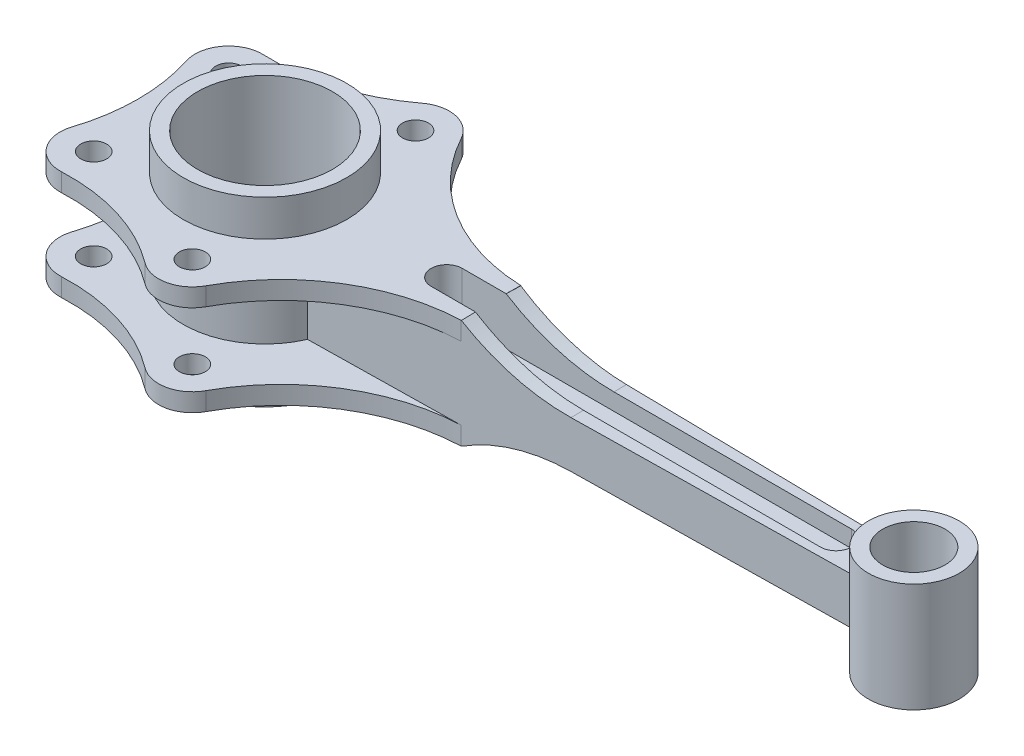
SolidWorks part; units mm, degrees
ref_plane "Front Plane" through (0, 0, 0) normal (0, 0, 1) x (1, 0, 0)
ref_plane "Top Plane" through (0, 0, 0) normal (0, 1, 0) x (1, 0, 0)
ref_plane "Right Plane" through (0, 0, 0) normal (1, 0, 0) x (0, 0, -1)
sketch "Sketch1" plane through (0, 0, 0) normal (0, 0, 1) x (1, 0, 0)
  line L0 (0, 35) -> (0, -35)
  point P0 (0, 0)
  point P7 (0, 0)
  dimension "D3" = 70
sweep "Sweep2" add path "Sketch1" circular profile diameter 63 parameters "D3"=63
sketch "Sketch22" plane through (0, 0, 0) normal (0, 1, 0) x (1, 0, 0)
  line L0 (0, 0) -> (74.8431, 0) construction
  line L1 (0, 13) -> (240, 9)
  line L2 (0, 13) -> (0, -13)
  line L3 (0, -13) -> (240, -9)
  line L5 (240, 9) -> (240, -9)
  point P4 (0, 0)
  point P8 (221.7079, 9)
  dimension "D1" = 26
  dimension "D2" = 18
  dimension "D3" = 240
extrude "Boss-Extrude2" add sketch "Sketch22" along normal mid plane 42
sketch "Sketch34" plane through (0.2166, 0, 12.9964) normal (0.0167, 0, 0.9999) x (0.9999, 0, -0.0167)
  line L0 (28.6932, 21) -> (239.8167, 21) construction
  line L1 (87, 21) -> (243, 21)
  line L2 (128.5692, 9) -> (243, 9)
  line L3 (128.5692, -9) -> (243, -9)
  line L4 (243, 9) -> (243, 21)
  line L5 (0, 0) -> (47.7774, 0) construction
  line L9 (243, -9) -> (243, -21)
  line L10 (87, -21) -> (243, -21)
  arc A0 (87, 21) -> (128.5692, 9) centre (128.5692, 87) ccw
  arc A2 (87, -21) -> (128.5692, -9) centre (128.5692, -87) cw
  point P8 (239.8167, 9)
  point P9 (0, 0)
  point P16 (239.8167, 9)
  point P17 (0, 0)
  point P18 (0, 0)
  point P19 (0, 0)
  dimension "D1" = 87
  dimension "D2" = 78
  dimension "D3" = 9
  dimension "D4" = 156
extrude "Cut-Extrude4" cut sketch "Sketch34" against normal up to next
sketch "Sketch35" plane through (0, 0, 0) normal (0, 0, 1) x (1, 0, 0)
  line L0 (250, 21) -> (250, -21)
  point P2 (250, 0)
  dimension "D1" = 42
  dimension "D2" = 250
sweep "Sweep4" add path "Sketch35" circular profile diameter 35 parameters "D3"=35
sketch "Sketch43" plane through (0, 0, 0) normal (0, 1, 0) x (1, 0, 0)
  line L0 (70, 0) -> (220, 0) construction
  line L1 (70, 6) -> (220, 6)
  line L2 (70, -6) -> (220, -6)
  arc A0 (70, 6) -> (70, -6) centre (70, 0) ccw
  arc A1 (220, -6) -> (220, 6) centre (220, 0) ccw
  circle A2 centre (250, 0) radius 17.5 construction
  circle A3 centre (250, 0) radius 17.5 construction
  point P3 (145, 0)
  dimension "D2" = 6
  dimension "D1" = 150
  dimension "D3" = 30
extrude "Cut-Extrude5" cut sketch "Sketch43" along normal up to next from offset 2.5
mirror "Mirror2" about plane through (0, 0, 0) normal (0, 1, 0) of "Cut-Extrude5"
sketch "Sketch47" plane through (0, 0, 0) normal (0, 1, 0) x (1, 0, 0)
  line L0 (0, 0) -> (17.8892, 0) construction
  line L1 (87, -6) -> (87, -11.55)
  line L2 (70, -6) -> (220, -6) construction
  line L3 (86.9121, 6) -> (70, 6) construction
  line L4 (70, -6) -> (87, -6)
  line L5 (86.9121, 6) -> (70, 6)
  line L6 (87.2045, -11.5466) -> (128.768, -10.8539) construction
  line L7 (87, 11.55) -> (86.9121, 6)
  arc A0 (-39.4063, 38.9864) -> (-52.3769, 22.0235) centre (-40, 26) ccw
  arc A1 (26.4296, 49.1938) -> (7.1819, 53.3864) centre (15, 43) ccw
  arc A2 (26.4296, -49.1938) -> (7.1819, -53.3864) centre (15, -43) cw
  arc A3 (-39.4063, -38.9864) -> (-52.3769, -22.0235) centre (-40, -26) cw
  arc A4 (-39.4063, 38.9864) -> (7.1819, 53.3864) centre (-36.118, 110.9113) ccw
  arc A5 (-52.3769, 22.0235) -> (-52.3769, -22.0235) centre (-120.9259, 0) cw
  arc A6 (-39.4063, -38.9864) -> (7.1819, -53.3864) centre (-36.118, -110.9113) cw
  arc A7 (26.4296, 49.1938) -> (87, 11.55) centre (89.7322, 83.4981) ccw
  arc A8 (70, 6) -> (70, -6) centre (70, 0) ccw construction
  arc A9 (70, 6) -> (70, -6) centre (70, 0) ccw
  arc A10 (26.4296, -49.1938) -> (87, -11.55) centre (89.7322, -83.4981) cw
  circle A11 centre (15, 43) radius 5
  circle A12 centre (-40, 26) radius 5
  circle A13 centre (-40, -26) radius 5
  circle A14 centre (15, -43) radius 5
  dimension "D1" = 15
  dimension "D5" = 13
  dimension "D6" = 72
  dimension "D7" = 87
  dimension "D8" = 72
  dimension "D9" = 10
  dimension "D2" = 40
  dimension "D3" = 26
  dimension "D4" = 17
extrude "Boss-Extrude5" add sketch "Sketch47" against normal blind 7 from surface starting at face at (67.8067, 21, -0.0008)
extrude "Boss-Extrude6" add sketch "Sketch47<3>" along normal blind 7 from surface starting at face at (67.8067, -21, -0.0008)
sketch "Sketch47<3>" plane through (0, 0, 0) normal (0, 1, 0) x (1, 0, 0) same geometry as "Sketch47"
sweep "Cut-Sweep1" cut path "Sketch1<4>" circular profile diameter 52 parameters "D3"=52
sketch "Sketch1<4>" plane through (0, 0, 0) normal (0, 0, 1) x (1, 0, 0) same geometry as "Sketch1"
sweep "Cut-Sweep2" cut path "Sketch35<2>" circular profile diameter 24 parameters "D3"=24
sketch "Sketch35<2>" plane through (0, 0, 0) normal (0, 0, 1) x (1, 0, 0) same geometry as "Sketch35"
